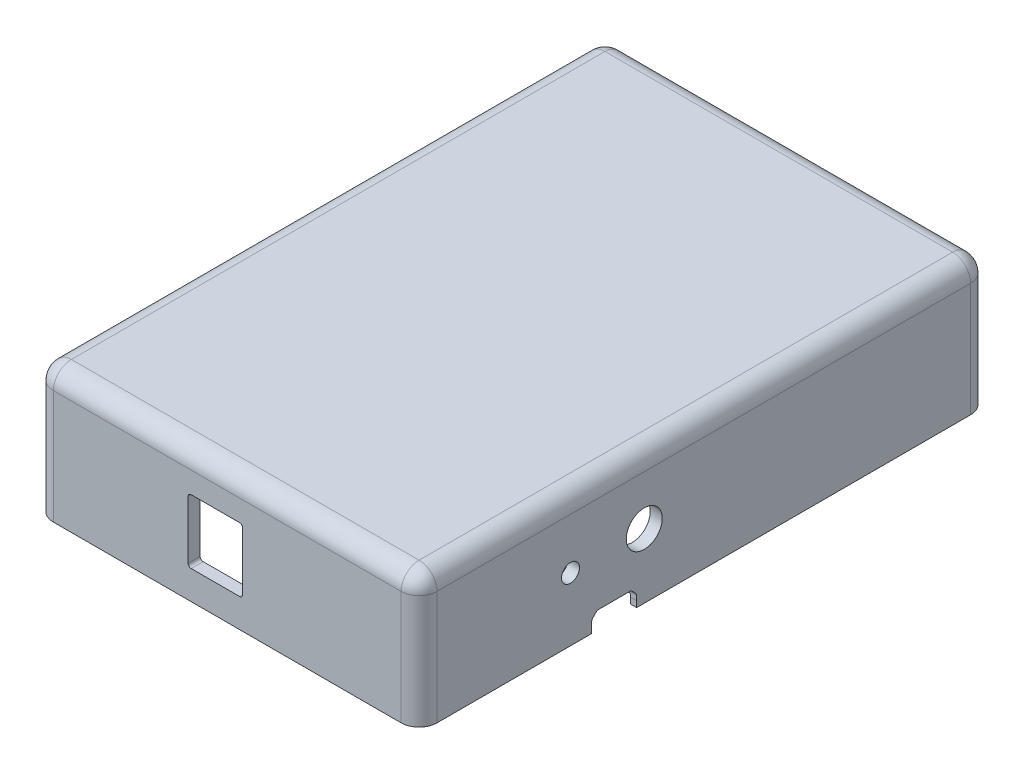
SolidWorks part; units mm, degrees
ref_plane "Front Plane" through (0, 0, 0) normal (0, 0, 1) x (1, 0, 0)
ref_plane "Top Plane" through (0, 0, 0) normal (0, 1, 0) x (1, 0, 0)
ref_plane "Right Plane" through (0, 0, 0) normal (1, 0, 0) x (0, 0, -1)
sketch "Sketch1" plane through (0, 0, 0) normal (0, 1, 0) x (1, 0, 0)
  line L5 (-32, -47.5) -> (32, -47.5)
  line L6 (-32, -47.5) -> (-32, 47.5)
  line L7 (-32, 47.5) -> (32, 47.5)
  line L8 (32, -47.5) -> (32, 47.5)
  line L9 (-32, -47.5) -> (32, 47.5) construction
  line L10 (-32, 47.5) -> (32, -47.5) construction
  point P0 (0, 0)
  dimension "D1" = 64
  dimension "D2" = 95
extrude "Boss-Extrude1" add sketch "Sketch1" along normal blind 2
sketch3d "3DSketch3"
  line L0 (-30, 0, 45.5) -> (-30, 0, -45.5)
  line L1 (-30, 0, -45.5) -> (30, 0, -45.5)
  line L2 (30, 0, -45.5) -> (30, 0, 45.5)
  line L3 (30, 0, 45.5) -> (-30, 0, 45.5)
  line L4 (-30, 0, 45.5) -> (-30, 0, -45.5)
  line L5 (-30, 0, -45.5) -> (30, 0, -45.5)
  line L6 (30, 0, -45.5) -> (30, 0, 45.5)
  line L7 (30, 0, 45.5) -> (-30, 0, 45.5)
  line L9 (-32, 0, 47.5) -> (-32, 0, -47.5)
  line L10 (-32, 0, 47.5) -> (32, 0, 47.5)
  line L11 (32, 0, 47.5) -> (32, 0, -47.5)
  line L12 (-32, 0, -47.5) -> (32, 0, -47.5)
  dimension "D1" = 2
extrude "Boss-Extrude2" add sketch "3DSketch3" along direction (0, -1, 0) on the side against the normal blind 20 contours L10 L9 L12 L11 | L4 L5 L6 L7
sketch "Sketch2" plane through (0, -20, 0) normal (0, -1, 0) x (1, 0, 0)
  line L8 (31, 46.5) -> (-31, 46.5)
  line L9 (-31, 46.5) -> (-31, -46.5)
  line L10 (-31, -46.5) -> (31, -46.5)
  line L11 (31, -46.5) -> (31, 46.5)
  line L12 (31, 46.5) -> (-31, 46.5)
  line L13 (-31, 46.5) -> (-31, -46.5)
  line L14 (-31, -46.5) -> (31, -46.5)
  line L15 (31, -46.5) -> (31, 46.5)
  dimension "D1" = 1
extrude "Cut-Extrude1" cut sketch "Sketch2" against normal blind 1.5
fillet "Fillet1" radius 10 4 edges
sketch "Sketch11" plane through (0, 0, -47.5) normal (0, 0, -1) x (-1, 0, 0)
  line L0 (32, -20) -> (-32, -20) construction
  circle A0 centre (0, -20) radius 4
extrude "Cut-Extrude5" cut sketch "Sketch11" against normal up to next
sketch "Sketch13" plane through (0, 0, 0) normal (0, -1, 0) x (1, 0, 0)
  line L0 (30, -35.5) -> (30, 35.5) construction
  line L1 (15.25, -43.07) -> (-25.25, -43.07)
  line L2 (15.25, -43.07) -> (15.25, -34.57)
  line L3 (15.25, -34.57) -> (-25.25, -34.57)
  line L4 (-25.25, -43.07) -> (-25.25, -34.57)
  line L5 (-20, -45.5) -> (20, -45.5) construction
  line L6 (12.75, -40.57) -> (12.75, -37.07)
  line L7 (12.75, -37.07) -> (-22.75, -37.07)
  line L8 (-22.75, -40.57) -> (-22.75, -37.07)
  line L9 (12.75, -40.57) -> (-22.75, -40.57)
  dimension "D1" = 14.75
  dimension "D2" = 2.43
  dimension "D3" = 40.5
  dimension "D4" = 8.5
  dimension "D5" = 2.5
extrude "Boss-Extrude4" add sketch "Sketch13" along normal blind 20
sketch "Sketch15" plane through (0, 0, 0) normal (0, -1, 0) x (1, 0, 0)
  line L1 (-22.75, -37.07) -> (12.75, -37.07)
  line L2 (-22.75, -37.07) -> (-22.75, -40.57)
  line L3 (-22.75, -40.57) -> (12.75, -40.57)
  line L4 (12.75, -37.07) -> (12.75, -40.57)
extrude "Boss-Extrude5" add sketch "Sketch15" along normal blind 11
sketch "Sketch17" plane through (0, 0, -34.57) normal (0, 0, 1) x (1, 0, 0)
  line L0 (15.25, -20) -> (-25.25, -20) construction
  line L1 (4.75, -20) -> (-15.25, -20)
  line L2 (4.75, -20) -> (4.75, -15.5)
  line L3 (4.75, -15.5) -> (-15.25, -15.5)
  line L4 (-15.25, -20) -> (-15.25, -15.5)
  line L5 (15.25, -20) -> (15.25, 0) construction
  dimension "D1" = 4.5
  dimension "D2" = 20
  dimension "D3" = 10.5
extrude "Cut-Extrude6" cut sketch "Sketch17" against normal blind 9
chamfer "Chamfer4" distance 4.2 angle 45 1 edges at (-15.25, -20, -35.82)
sketch "Sketch18" plane through (0, 0, 0) normal (0, -1, 0) x (1, 0, 0)
  line L6 (-31, 46.5) -> (-16, 31.5) construction
  line L11 (16, -31.5) -> (31, -46.5) construction
  circle A1 centre (-25.6575, 41.1575) radius 1.5
  circle A2 centre (25.6575, -41.1575) radius 5
  circle A3 centre (25.6575, -41.1575) radius 1.5
  circle A6 centre (-25.6575, 41.1575) radius 5
  point P0 (0, 0)
  dimension "D1" = 21.9203
  dimension "D5" = 48.5
  dimension "D6" = 48.5
extrude "Boss-Extrude6" add sketch "Sketch18" along normal up to surface (18.5 mm away) up to face at (0, -18.5, -11.5)
fillet "Fillet2" radius 3 4 edges
fillet "Fillet3" radius 3 8 edges at (-32, 2, 0) (-31.1213, 2, -46.6213) (0, 2, -47.5) (31.1213, 2, -46.6213) (32, 2, 0) (31.1213, 2, 46.6213) (0, 2, 47.5) (-31.1213, 2, 46.6213)
sketch "Sketch20" plane through (0, 0, 0) normal (0, -1, 0) x (1, 0, 0)
  line L0 (4.75, -43.07) -> (15.25, -43.07) construction
  line L1 (10, -43.07) -> (13, -43.07)
  line L2 (10, -43.07) -> (10, -45.5)
  line L3 (10, -45.5) -> (13, -45.5)
  line L4 (13, -43.07) -> (13, -45.5)
  line L5 (20, -45.5) -> (3.7081, -45.5) construction
  line L6 (-25.25, -43.07) -> (-15.25, -43.07) construction
  line L7 (-20.25, -43.07) -> (-17.25, -43.07)
  line L8 (-20.25, -43.07) -> (-20.25, -45.5)
  line L9 (-20.25, -45.5) -> (-17.25, -45.5)
  line L10 (-17.25, -43.07) -> (-17.25, -45.5)
  line L11 (-3.7081, -45.5) -> (-20, -45.5) construction
  dimension "D1" = 3
  dimension "D2" = 3
extrude "Boss-Extrude7" add sketch "Sketch20" along normal up to surface (18.5 mm away) up to face at (0, -18.5, -9.2)
fillet "Fillet6" radius 1 4 edges at (-20.25, -9.25, -43.07) (10, -9.25, -43.07) (13, -9.25, -43.07) (-17.25, -9.25, -43.07)
fillet "Fillet7" radius 2 3 edges at (-25.25, 0, -38.82) (15.25, 0, -38.82) (-5, 0, -34.57)
sketch "Sketch21" plane through (0, 0, 0) normal (0, -1, 0) x (-1, 0, 0)
  circle A0 centre (-26, -0.9501) radius 1.5
  circle A1 centre (-26, -0.9501) radius 3.25
  dimension "D1" = 3
  dimension "D2" = 6.5
extrude "Boss-Extrude8" add sketch "Sketch21" along normal blind 3
pattern_linear "LPattern1" count 2 spacing 52 along (-1, 0, 0) of "Boss-Extrude8"
sketch "Sketch22" plane through (0, 0, 0) normal (0, -1, 0) x (1, 0, 0)
  circle A0 centre (20.5, 38.9501) radius 1
  circle A1 centre (20.5, 38.9501) radius 2.5
  dimension "D1" = 2
  dimension "D2" = 5
extrude "Boss-Extrude9" add sketch "Sketch22" along normal blind 3
sketch "Sketch23" plane through (0, 0, 0) normal (0, -1, 0) x (1, 0, 0)
  arc A0 (-29.645, 38.1409) -> (-22.6409, 45.145) centre (-25.6575, 41.1575) ccw
  arc A1 (-29.645, 38.1409) -> (-22.6409, 45.145) centre (-22.6409, 38.1409) cw
extrude "Cut-Extrude11" cut sketch "Sketch23" along normal blind 7
pattern_linear "LPattern3" count 2 spacing 41 along (-1, 0, 0) of "Boss-Extrude9"
sketch "Sketch26" plane through (-32, 0, 0) normal (-1, 0, 0) x (0, 0, 1)
  line L1 (-26.6038, -6.1779) -> (-12.6038, -6.1779)
  line L2 (-26.6038, -6.1779) -> (-26.6038, -15.3779)
  line L3 (-26.6038, -15.3779) -> (-12.6038, -15.3779)
  line L4 (-12.6038, -6.1779) -> (-12.6038, -15.3779)
  dimension "D1" = 14
  dimension "D2" = 9.2
extrude "Cut-Extrude15" cut sketch "Sketch26" against normal blind 7
sketch "Sketch27" plane through (32, 0, 0) normal (1, 0, 0) x (0, 0, -1)
  line L0 (-11.9648, -17.2511) -> (-11.3612, -17.8546)
  line L1 (-11.2001, -18.2436) -> (-11.2001, -18.99)
  line L2 (-11.7501, -19.4416) -> (-11.7501, -19.6287) construction
  line L3 (-11.7501, -19.5351) -> (-18.1501, -19.5351)
  line L4 (-18.1501, -19.6287) -> (-18.1501, -19.4416) construction
  line L5 (-18.7001, -18.99) -> (-18.7001, -18.2436)
  line L6 (-18.539, -17.8546) -> (-17.9355, -17.2511)
  line L7 (-0.4501, -17.09) -> (-29.4501, -17.09) construction
  line L8 (-17.5466, -17.09) -> (-12.4019, -17.09)
  line L9 (-12.3537, -17.09) -> (-12.4501, -17.09) construction
  arc A0 (-11.3612, -17.8546) -> (-11.2001, -18.2436) centre (-11.7501, -18.2436) cw
  arc A1 (-11.2001, -18.99) -> (-11.7501, -19.5351) centre (-11.7453, -18.99) cw
  arc A2 (-18.1501, -19.5351) -> (-18.7001, -18.99) centre (-18.1501, -18.9851) cw
  arc A3 (-18.539, -17.8546) -> (-18.7001, -18.2436) centre (-18.1501, -18.2436) ccw construction
  arc A4 (-18.7001, -18.2436) -> (-18.539, -17.8546) centre (-18.1501, -18.2436) cw
  arc A5 (-17.9355, -17.2511) -> (-17.5466, -17.09) centre (-17.5466, -17.64) cw
  arc A6 (-17.5466, -17.09) -> (-17.9355, -17.2511) centre (-17.5466, -17.64) ccw construction
  arc A7 (-12.4019, -17.09) -> (-11.9648, -17.2511) centre (-12.3579, -17.6442) cw
extrude "Cut-Extrude16" cut sketch "Sketch27" against normal blind 2
sketch "Sketch28" plane through (0, -20, 0) normal (0, -1, 0) x (1, 0, 0)
  line L1 (32, 11.2001) -> (31, 11.2001)
  line L2 (32, 11.2001) -> (32, 18.7001)
  line L3 (32, 18.7001) -> (31, 18.7001)
  line L4 (31, 11.2001) -> (31, 18.7001)
extrude "Cut-Extrude17" cut sketch "Sketch28" against normal blind 1
sketch "Sketch29" plane through (32, 0, 0) normal (1, 0, 0) x (0, 0, -1)
  line L0 (-19.3001, -9.45) -> (-25.2001, -9.45) construction
  circle A0 centre (-22.2501, -9.45) radius 1.5
  dimension "D1" = 3
extrude "Cut-Extrude18" cut sketch "Sketch29" against normal blind 3
sketch "Sketch30" plane through (32, 0, 0) normal (1, 0, 0) x (0, 0, -1)
  circle A0 centre (-9.9387, -9.223) radius 3
  dimension "D1" = 6
extrude "Cut-Extrude19" cut sketch "Sketch30" against normal blind 3
sketch "Sketch32" plane through (0, 0, 47.5) normal (0, 0, 1) x (1, 0, 0)
  line L0 (23.5, -4.55) -> (-23.5, -4.55) construction
  line L1 (2.0627, -15.2134) -> (-6.0227, -15.2134)
  line L2 (2.5627, -14.7134) -> (2.5627, -5.05)
  line L3 (2.0627, -4.55) -> (-6.0227, -4.55)
  line L4 (-6.5227, -14.7134) -> (-6.5227, -5.05)
  arc A0 (2.5627, -5.05) -> (2.0627, -4.55) centre (2.0627, -5.05) ccw
  arc A1 (-6.0227, -4.55) -> (-6.5227, -5.05) centre (-6.0227, -5.05) ccw
  arc A2 (-6.0227, -15.2134) -> (-6.5227, -14.7134) centre (-6.0227, -14.7134) cw
  arc A3 (2.0627, -15.2134) -> (2.5627, -14.7134) centre (2.0627, -14.7134) ccw
  point P10 (-6.5227, -4.55)
  dimension "D1" = 0.5
extrude "Cut-Extrude21" cut sketch "Sketch32" against normal blind 3
fillet "Fillet8" radius 5 4 edges at (-31, -19.25, 46.5) (31, -19.25, 46.5) (31, -19.25, -46.5) (-31, -19.25, -46.5)
fillet "Fillet9" radius 0.5 1 edges at (-22.122, -7, 37.622)
sketch "Sketch34" plane through (0, 0, 0) normal (0, -1, 0) x (1, 0, 0)
  circle A0 centre (-26, 0.9501) radius 1.5
extrude "Boss-Extrude10" add sketch "Sketch34" along normal blind 7
pattern_linear "LPattern4" count 2 spacing 52 along (1, 0, 0) of "Boss-Extrude10"
sketch "Sketch35" plane through (0, 0, 0) normal (0, -1, 0) x (1, 0, 0)
  circle A0 centre (20.5, 38.9501) radius 1
extrude "Boss-Extrude11" add sketch "Sketch35" along normal blind 5
pattern_linear "LPattern5" count 2 spacing 41 along (-1, 0, 0) of "Boss-Extrude11"
